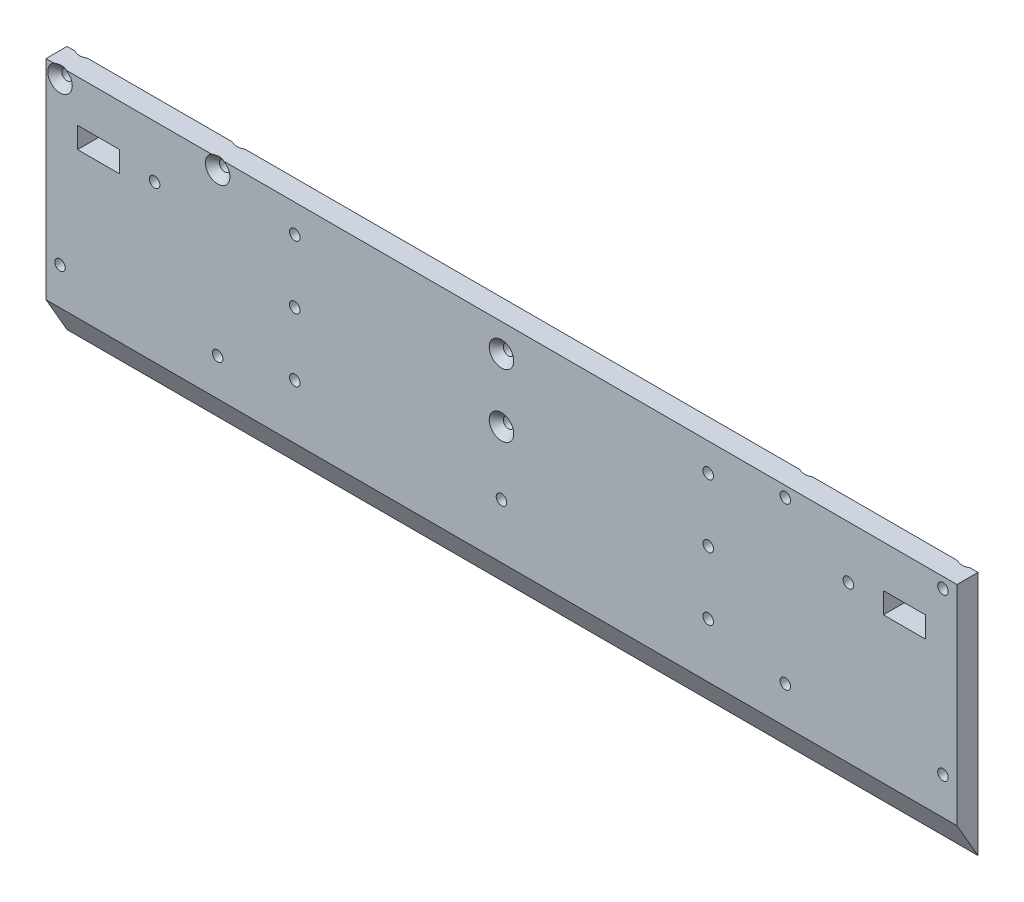
SolidWorks part; units mm, degrees
ref_plane "Front" through (0, 0, 0) normal (0, 0, 1) x (1, 0, 0)
ref_plane "Top" through (0, 0, 0) normal (0, 1, 0) x (1, 0, 0)
ref_plane "Right" through (0, 0, 0) normal (1, 0, 0) x (0, 0, -1)
sketch "草图1" plane through (0, 0, 0) normal (0, 0, 1) x (1, 0, 0)
  line L1 (-130, 35) -> (130, 35)
  line L2 (-130, 35) -> (-130, -35)
  line L3 (-130, -35) -> (130, -35)
  line L4 (130, 35) -> (130, -35)
  line L5 (-130, 35) -> (130, -35) construction
  line L6 (-130, -35) -> (130, 35) construction
  point P0 (0, 0)
extrude "凸台-拉伸1" add sketch "草图1" along normal blind 6
sketch "草图2" plane through (130, 0, 0) normal (1, 0, 0) x (0, 0, -1)
  line L0 (0, -35) -> (-6, -24.6077)
  line L1 (-6, -24.6077) -> (-6, -35)
  line L2 (-6, -35) -> (-6, 35) construction
  line L3 (-6, -35) -> (0, -35)
extrude "切除-拉伸1" cut sketch "草图2" against normal blind 260
sketch "草图3" plane through (0, 0, 6) normal (0, 0, 1) x (1, 0, 0)
  circle A1 centre (-59, 9) radius 1.5
  circle A2 centre (59, 9) radius 1.5
extrude "切除-拉伸2" cut sketch "草图3" against normal blind 10
sketch "草图4" plane through (0, 0, 0) normal (0, 0, -1) x (-1, 0, 0)
  circle A1 centre (-59, 27) radius 1.5
  circle A2 centre (-59, -9) radius 1.5
  circle A4 centre (59, 27) radius 1.5
  circle A5 centre (59, -9) radius 1.5
extrude "切除-拉伸3" cut sketch "草图4" against normal blind 10
sketch "草图5" plane through (0, 0, 6) normal (0, 0, 1) x (1, 0, 0)
  circle A0 centre (0, 27) radius 1.5
  circle A1 centre (0, 9) radius 1.5
  circle A2 centre (0, -9) radius 1.5
extrude "切除-拉伸4" cut sketch "草图5" against normal blind 33
sketch "草图6" plane through (0, 0, 6) normal (0, 0, 1) x (1, 0, 0)
  line L4 (-121, 23) -> (-109, 23)
  line L5 (-121, 23) -> (-121, 17)
  line L6 (-121, 17) -> (-109, 17)
  line L7 (-109, 23) -> (-109, 17)
  line L8 (-121, 23) -> (-109, 17) construction
  line L9 (-121, 17) -> (-109, 23) construction
  circle A0 centre (-99, 20) radius 1.5
extrude "切除-拉伸5" cut sketch "草图6" against normal blind 10
mirror "镜向1" about plane through (0, 0, 0) normal (1, 0, 0) of "切除-拉伸5"
sketch "草图7" plane through (0, 0, 6) normal (0, 0, 1) x (1, 0, 0)
  circle A0 centre (-126, 32) radius 1.5
  circle A1 centre (-81, 32) radius 1.5
  circle A2 centre (-81, -14) radius 1.5
  circle A3 centre (-126, -14) radius 1.5
extrude "切除-拉伸6" cut sketch "草图7" against normal blind 10
mirror "镜向2" about plane through (0, 0, 0) normal (1, 0, 0) of "切除-拉伸6"
chamfer "倒角1" distance 2 angle 45 1 edges at (127.5, 32, 0)
chamfer "倒角2" distance 2 angle 45 8 edges at (-124.5, 32, 0) (-124.5, 32, 6) (-79.5, 32, 0) (-79.5, 32, 6) (-60.5, 27, 0) (1.5, 27, 6) (57.5, 27, 0) (82.5, 32, 0)
chamfer "倒角3" distance 2 angle 45 11 edges at (1.5, 9, 0) (1.5, 9, 6) (-124.5, -14, 0) (-79.5, -14, 0) (-60.5, -9, 0) (-97.5, 20, 0) (-57.5, 9, 0) (1.5, -9, 0) (1.5, 27, 0) (60.5, 9, 0) (100.5, 20, 0)
chamfer "倒角4" distance 2 angle 45 3 edges at (57.5, -9, 0) (82.5, -14, 0) (127.5, -14, 0)
